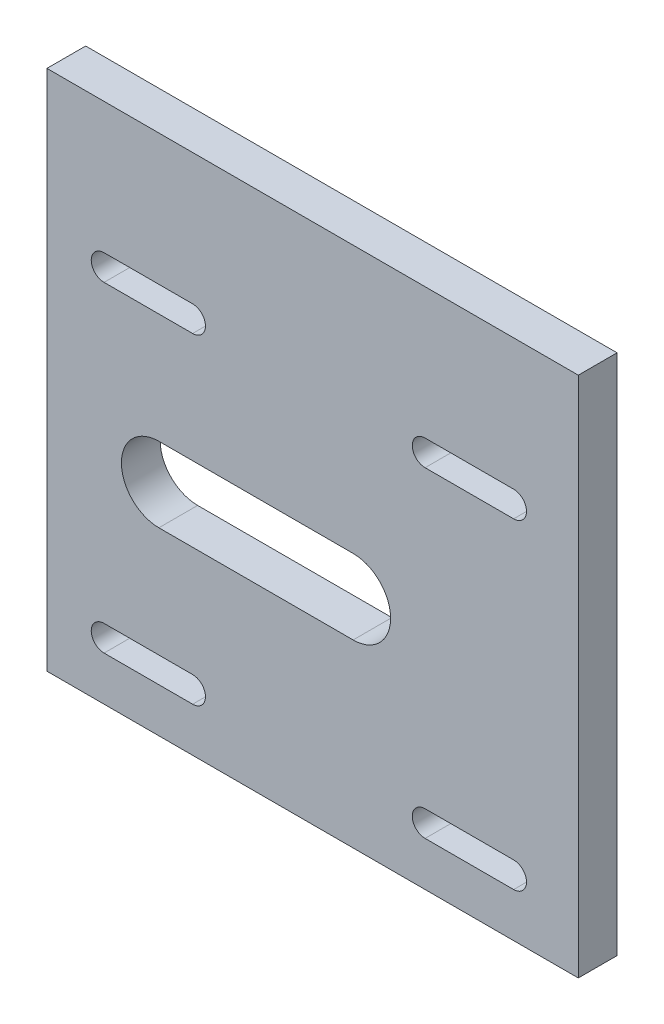
SolidWorks part; units mm, degrees
ref_plane "Front Plane" through (0, 0, 0) normal (0, 0, 1) x (1, 0, 0)
ref_plane "Top Plane" through (0, 0, 0) normal (0, 1, 0) x (1, 0, 0)
ref_plane "Right Plane" through (0, 0, 0) normal (1, 0, 0) x (0, 0, -1)
sketch "Sketch1" plane through (0, 0, 0) normal (0, 0, 1) x (1, 0, 0)
  line L1 (-132.1572, 31.4462) -> (-284.5572, 31.4462)
  line L2 (-132.1572, 31.4462) -> (-132.1572, -118.2868)
  line L3 (-132.1572, -118.2868) -> (-284.5572, -118.2868)
  line L4 (-284.5572, 31.4462) -> (-284.5572, -118.2868)
  line L5 (-242.7742, -101.9038) -> (-268.1742, -101.9038) construction
  line L6 (-242.7742, -105.5868) -> (-268.1742, -105.5868)
  line L7 (-242.7742, -98.2208) -> (-268.1742, -98.2208)
  line L8 (-242.7742, -9.8288) -> (-268.1742, -9.8288) construction
  line L9 (-242.7742, -13.5118) -> (-268.1742, -13.5118)
  line L10 (-242.7742, -6.1458) -> (-268.1742, -6.1458)
  line L11 (-150.6992, -9.8288) -> (-176.0992, -9.8288) construction
  line L12 (-150.6992, -13.5118) -> (-176.0992, -13.5118)
  line L13 (-150.6992, -6.1458) -> (-176.0992, -6.1458)
  line L14 (-150.6992, -101.9038) -> (-176.0992, -101.9038) construction
  line L15 (-150.6992, -105.5868) -> (-176.0992, -105.5868)
  line L16 (-150.6992, -98.2208) -> (-176.0992, -98.2208)
  line L17 (-196.7367, -55.8663) -> (-252.4523, -55.8663) construction
  line L18 (-196.7367, -66.6107) -> (-252.4523, -66.6107)
  line L19 (-196.7367, -45.122) -> (-252.4523, -45.122)
  line L20 (49.2125, 31.4462) -> (-99.8992, 31.4462) construction
  circle A1 centre (-150.6992, -101.9038) radius 2.413 construction
  circle A2 centre (-150.6992, -101.9038) radius 2.413 construction
  circle A3 centre (-150.6992, -101.9038) radius 3.683 construction
  circle A4 centre (-242.7742, -101.9038) radius 3.683 construction
  circle A5 centre (-242.7742, -9.8288) radius 3.683 construction
  circle A6 centre (-150.6992, -9.8288) radius 3.683 construction
  arc A7 (-242.7742, -105.5868) -> (-242.7742, -98.2208) centre (-242.7742, -101.9038) ccw
  arc A8 (-268.1742, -98.2208) -> (-268.1742, -105.5868) centre (-268.1742, -101.9038) ccw
  arc A9 (-242.7742, -13.5118) -> (-242.7742, -6.1458) centre (-242.7742, -9.8288) ccw
  arc A10 (-268.1742, -6.1458) -> (-268.1742, -13.5118) centre (-268.1742, -9.8288) ccw
  arc A11 (-150.6992, -13.5118) -> (-150.6992, -6.1458) centre (-150.6992, -9.8288) ccw
  arc A12 (-176.0992, -6.1458) -> (-176.0992, -13.5118) centre (-176.0992, -9.8288) ccw
  arc A13 (-150.6992, -105.5868) -> (-150.6992, -98.2208) centre (-150.6992, -101.9038) ccw
  arc A14 (-176.0992, -98.2208) -> (-176.0992, -105.5868) centre (-176.0992, -101.9038) ccw
  arc A15 (-196.7367, -66.6107) -> (-196.7367, -45.122) centre (-196.7367, -55.8663) ccw
  arc A16 (-252.4523, -45.122) -> (-252.4523, -66.6107) centre (-252.4523, -55.8663) ccw
  point P25 (-255.4742, -101.9038)
  point P31 (-255.4742, -9.8288)
  point P37 (-163.3992, -9.8288)
  point P43 (-163.3992, -101.9038)
  point P51 (-224.5945, -55.8663)
  dimension "D1" = 152.4
  dimension "D2" = 1.27
  dimension "D3" = 12.7
  dimension "D4" = 25.4
  dimension "D5" = 12.7
extrude "Boss-Extrude1" add sketch "Sketch1" along normal blind 11.1125
